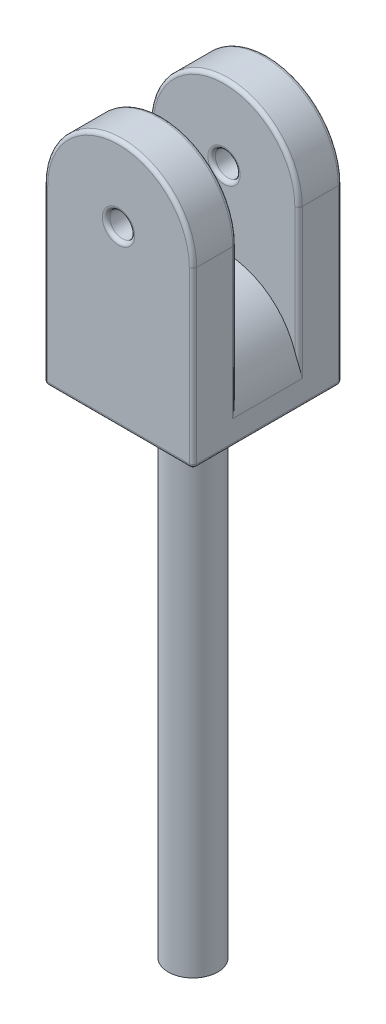
SolidWorks part; units mm, degrees
material "C-Glass Fiber"
ref_plane "Front Plane" through (0, 0, 0) normal (0, 0, 1) x (1, 0, 0)
ref_plane "Top Plane" through (0, 0, 0) normal (0, 1, 0) x (1, 0, 0)
ref_plane "Right Plane" through (0, 0, 0) normal (1, 0, 0) x (0, 0, -1)
sketch "Sketch1" plane through (0, 0, 0) normal (0, 1, 0) x (1, 0, 0)
  circle A0 centre (0, 0) radius 12.7
  dimension "D1" = 25.4
extrude "Boss-Extrude1" add sketch "Sketch1" along normal blind 254
sketch "Sketch2" plane through (0, 254, 0) normal (0, 1, 0) x (1, 0, 0)
  line L1 (-38.1, -38.1) -> (38.1, -38.1)
  line L2 (-38.1, -38.1) -> (-38.1, 38.1)
  line L3 (-38.1, 38.1) -> (38.1, 38.1)
  line L4 (38.1, -38.1) -> (38.1, 38.1)
  line L5 (-38.1, -38.1) -> (38.1, 38.1) construction
  line L6 (-38.1, 38.1) -> (38.1, -38.1) construction
  point P0 (0, 0)
  dimension "D1" = 76.2
  dimension "D2" = 76.2
extrude "Boss-Extrude2" add sketch "Sketch2" along normal blind 127
fillet "Fillet1" 2 edges at (-38.1, 381, 0) (38.1, 381, 0) type full round first side face at (-38.1, 317.5, 0) second side face at (38.1, 317.5, 0) middle face at (0, 381, 0)
sketch "Sketch3" plane through (0, 0, 0) normal (1, 0, 0) x (0, 0, -1)
  line L0 (38.1, 381) -> (-38.1, 381) construction
  line L1 (-15.875, 381) -> (15.875, 381)
  line L2 (-15.875, 381) -> (-15.875, 304.8)
  line L3 (-15.875, 304.8) -> (15.875, 304.8)
  line L4 (15.875, 381) -> (15.875, 304.8)
  dimension "D1" = 22.225
  dimension "D2" = 22.225
  dimension "D3" = 76.2
extrude "Cut-Extrude1" cut sketch "Sketch3" against normal mid plane 76.2
hole_wizard "Hole1" positions "Sketch4" profile "Sketch5" legacy end condition up to next
sketch "Sketch4" plane through (0, 0, 38.1) normal (0, 0, 1) x (1, 0, 0)
  point P0 (0, 342.9)
sketch "Sketch5" plane through (0, 342.9, 38.1) normal (1, 0, 0) x (0, -1, 0)
  line L0 (0, 0) -> (0, 76.2)
  line L1 (0, 76.2) -> (6.35, 76.2)
  line L2 (6.35, 76.2) -> (6.35, 0)
  line L3 (6.35, 0) -> (0, 0)
  line L4 (0, 110) -> (0, -10) construction
  dimension "Diameter" = 12.7
  dimension "Depth" = 76.2
mirror "Mirror1" about plane through (0, 0, 0) normal (0, 0, 1) of "Hole1"
fillet "Fillet2" 2 edges at (-38.1, 304.8, 0) (38.1, 304.8, 0) type full round first side face at (-38.1, 311.15, 0) second side face at (38.1, 311.15, 0) middle face at (0, 304.8, 0)
fillet "Fillet3" radius 1.905 20 edges at (-38.1, 304.8, -15.875) (0, 381, -15.875) (-38.1, 304.8, 15.875) (0, 381, 15.875) (-38.1, 298.45, -38.1) (0, 381, -38.1) (-38.1, 298.45, 38.1) (0, 381, 38.1) (38.1, 304.8, -15.875) (38.1, 304.8, 15.875) (-6.35, 342.9, -38.1) (6.35, 342.9, 38.1) (38.1, 298.45, -38.1) (38.1, 298.45, 38.1) (-38.1, 254, 0) (0, 254, -38.1) (38.1, 254, 0) (0, 254, 38.1) (0, 336.55, 15.875) (0, 349.25, -15.875)
